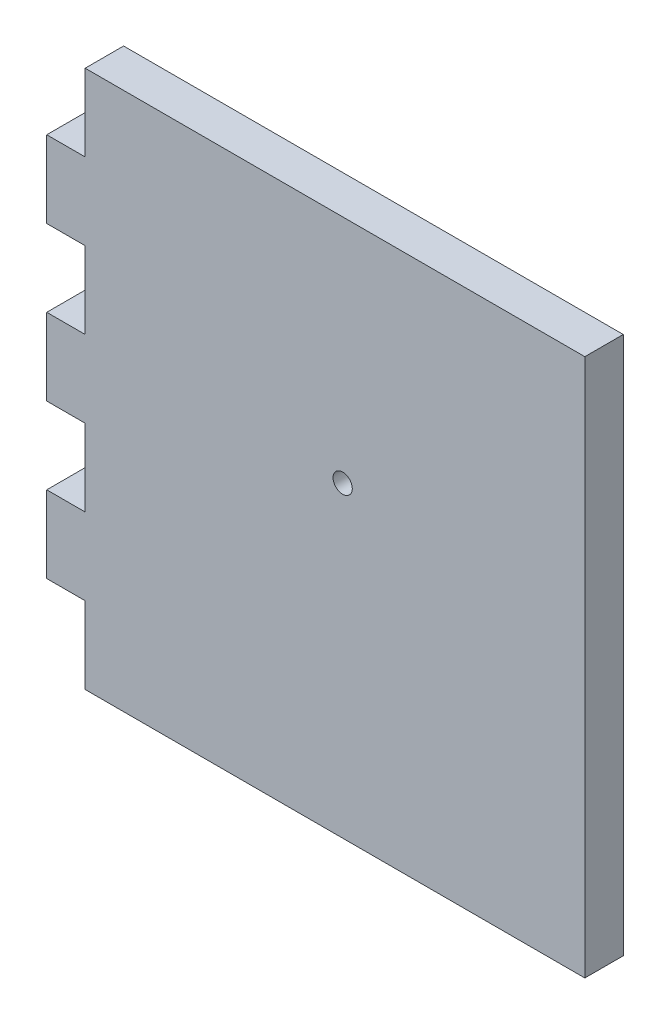
SolidWorks part; units mm, degrees
ref_plane "Front Plane" through (0, 0, 0) normal (0, 0, 1) x (1, 0, 0)
ref_plane "Top Plane" through (0, 0, 0) normal (0, 1, 0) x (1, 0, 0)
ref_plane "Right Plane" through (0, 0, 0) normal (1, 0, 0) x (0, 0, -1)
sketch "Sketch1" plane through (0, 0, 0) normal (0, 0, 1) x (1, 0, 0)
  line L1 (0, 0) -> (177.8, 0)
  line L2 (0, 0) -> (0, -177.8)
  line L3 (0, -177.8) -> (177.8, -177.8)
  line L4 (177.8, 0) -> (177.8, -177.8)
  dimension "D1" = 177.8
  dimension "D2" = 177.8
extrude "Boss-Extrude1" add sketch "Sketch1" along normal blind 12.7
sketch "Sketch2" plane through (0, 0, 12.7) normal (0, 0, 1) x (1, 0, 0)
  line L4 (0, 0) -> (0, -177.8)
  line L5 (0, -177.8) -> (177.8, -177.8)
  line L6 (177.8, -177.8) -> (177.8, 0)
  line L7 (177.8, 0) -> (0, 0)
  line L8 (0, 0) -> (0, -177.8)
  line L9 (0, -177.8) -> (177.8, -177.8)
  line L10 (177.8, -177.8) -> (177.8, 0)
  line L11 (177.8, 0) -> (0, 0)
  circle A0 centre (97.79, -76.2) radius 3.175
  dimension "D3" = 6.35
  dimension "D2" = 97.79
  dimension "D4" = 101.6
  dimension "D1" = 0
extrude "Cut-Extrude3" cut sketch "Sketch2" against normal through all contours A0
sketch "Sketch4" plane through (0, 0, 12.7) normal (0, 0, 1) x (1, 0, 0)
  line L0 (0, 0) -> (0, -177.8) construction
  line L1 (0, 0) -> (12.7, 0)
  line L2 (0, 0) -> (0, -25.4)
  line L3 (0, -25.4) -> (12.7, -25.4)
  line L4 (12.7, 0) -> (12.7, -25.4)
  line L5 (0, -50.8) -> (12.7, -50.8)
  line L6 (0, -50.8) -> (0, -76.2)
  line L7 (0, -76.2) -> (12.7, -76.2)
  line L8 (12.7, -50.8) -> (12.7, -76.2)
  line L9 (0, -76.2) -> (177.8, -76.2) construction
  line L10 (177.8, -177.8) -> (177.8, 0) construction
  line L12 (0, -101.6) -> (12.7, -101.6)
  line L13 (0, -101.6) -> (0, -127)
  line L14 (0, -127) -> (12.7, -127)
  line L15 (12.7, -101.6) -> (12.7, -127)
  line L16 (0, -177.8) -> (12.7, -177.8)
  line L17 (0, -177.8) -> (0, -152.4)
  line L18 (0, -152.4) -> (12.7, -152.4)
  line L19 (12.7, -177.8) -> (12.7, -152.4)
  dimension "D1" = 25.4
  dimension "D2" = 12.7
  dimension "D3" = 25.4
  dimension "D4" = 12.7
  dimension "D5" = 25.4
  dimension "D6" = 25.4
  dimension "D7" = 25.4
  dimension "D8" = 12.7
  dimension "D9" = 25.4
extrude "Cut-Extrude4" cut sketch "Sketch4" against normal through all contours L2 L1 L4 L3 | L6 L5 L8 L7 | L13 L12 L15 L14 | L17 L16 L19 L18
